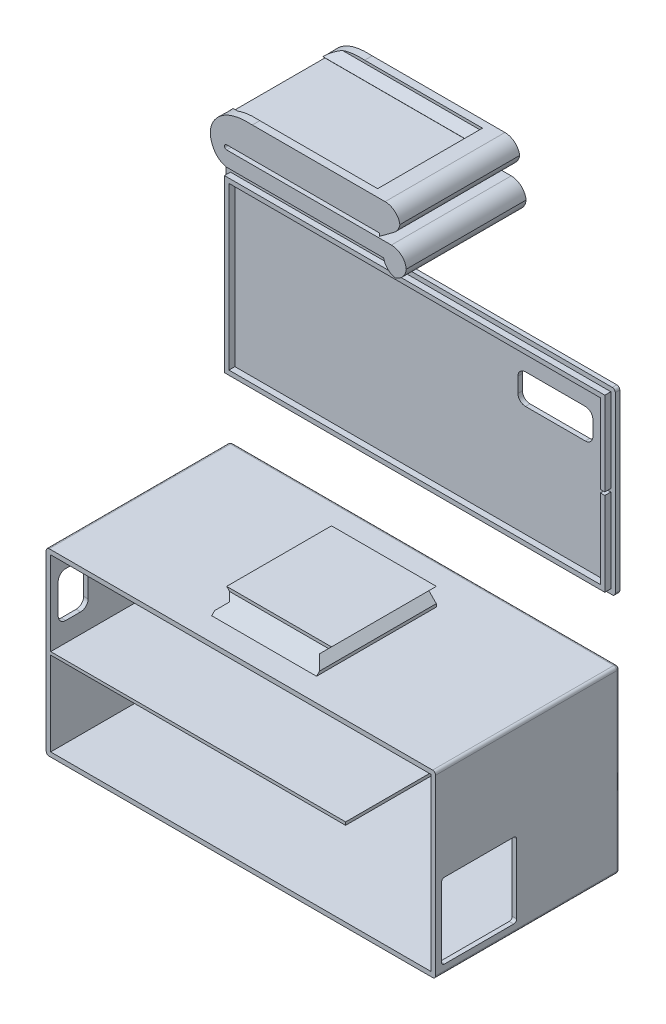
SolidWorks part; units mm, degrees
ref_plane "Alzado" through (0, 0, 0) normal (1, 0, 0) x (0, 1, 0)
ref_plane "Planta" through (0, 0, 0) normal (0, 0, 1) x (0, 1, 0)
ref_plane "Vista lateral" through (0, 0, 0) normal (0, 1, 0) x (-1, 0, 0)
sketch "Croquis1" plane through (0, 0, 0) normal (0, 0, 1) x (0, 1, 0)
  line L0 (0.5, 65) -> (0.5, -65) construction
  line L1 (30, -65) -> (-30, -65)
  line L2 (30, -65) -> (30, 65)
  line L3 (30, 65) -> (-30, 65)
  line L4 (-30, -65) -> (-30, 65)
  line L5 (30, -65) -> (-30, 65) construction
  line L6 (30, 65) -> (-30, -65) construction
  line L7 (-0.5, -65) -> (-0.5, 65) construction
  point P0 (0, 0)
  dimension "D1" = 60
  dimension "D2" = 130
  dimension "D3" = 1
  dimension "D4" = 29.5
extrude "Saliente-Extruir1" add sketch "Croquis1" along normal blind 1.5
sketch "Croquis2" plane through (0, 0, 1.5) normal (0, 0, 1) x (1, 0, 0)
  line L4 (-63.5, 0.5) -> (63.5, 0.5)
  line L5 (-63.5, -0.5) -> (63.5, -0.5)
  line L6 (-63.5, 28.5) -> (-63.5, 0.5)
  line L7 (-63.5, -28.5) -> (63.5, -28.5)
  line L8 (65, -30) -> (65, 30)
  line L9 (-65, -30) -> (65, -30)
  line L10 (-65, 30) -> (-65, -30)
  line L11 (65, 30) -> (-65, 30)
  line L12 (65, -30) -> (65, 30)
  line L13 (-65, -30) -> (65, -30)
  line L14 (-65, 30) -> (-65, -30)
  line L15 (65, 30) -> (-65, 30)
  line L16 (63.5, -28.5) -> (63.5, -0.5)
  line L17 (63.5, 28.5) -> (-63.5, 28.5)
  line L18 (-63.5, -0.5) -> (-63.5, -28.5)
  line L19 (63.5, 0.5) -> (63.5, 28.5)
  line L20 (-63.5, 28.5) -> (-63.5, -28.5) construction
  line L22 (63.5, -28.5) -> (63.5, 28.5) construction
  dimension "D3" = 1
  dimension "D1" = 0
  dimension "D2" = 1.5
extrude "Saliente-Extruir2" add sketch "Croquis2" along normal blind 60
sketch "Croquis3" plane through (0, 0.5, 0) normal (0, 1, 0) x (-1, 0, 0)
  line L1 (-63.5, 61.5) -> (-34.9603, 61.5)
  line L2 (-63.5, 61.5) -> (-63.5, 31.5)
  line L3 (-53.5, 21.5) -> (-44.9603, 21.5)
  line L4 (-34.9603, 61.5) -> (-34.9603, 31.5)
  arc A0 (-63.5, 31.5) -> (-53.5, 21.5) centre (-53.5, 31.5) ccw
  arc A1 (-44.9603, 21.5) -> (-34.9603, 31.5) centre (-44.9603, 31.5) ccw
  point P9 (-34.9603, 21.5)
  dimension "D2" = 10
  dimension "D1" = 40
extrude "Cortar-Extruir1" cut sketch "Croquis3" against normal blind 2
sketch "Croquis4" plane through (0, 0, 1.5) normal (0, 0, 1) x (1, 0, 0)
  line L0 (-63.5, -6.5) -> (63.5, -6.5)
  line L4 (-63.5, -0.5) -> (-63.5, -28.5) construction
  line L5 (63.5, -28.5) -> (63.5, 28.5) construction
  line L6 (34.9603, -0.5) -> (-63.5, -0.5) construction
  line L7 (-63.5, -8.1) -> (63.5, -8.1)
  line L8 (-63.5, -6.5) -> (-63.5, -0.5)
  line L9 (-63.5, -0.5) -> (63.5, -0.5)
  line L10 (63.5, -0.5) -> (63.5, -6.5)
  line L11 (-63.5, -8.1) -> (-63.5, -28.5)
  line L12 (-63.5, -28.5) -> (63.5, -28.5)
  line L13 (63.5, -28.5) -> (63.5, -8.1)
  dimension "D1" = 6
  dimension "D2" = 1.6
extrude "Saliente-Extruir3" add sketch "Croquis4" along normal blind 3
sketch "Croquis5" plane through (-65, 0, 0) normal (-1, 0, 0) x (0, -1, 0)
  line L0 (-14.5, 1.5) -> (-14.5, 61.5) construction
  line L1 (-28.5, 1.5) -> (-0.5, 1.5) construction
  line L2 (-30, 61.5) -> (30, 61.5) construction
  line L4 (-9.5, 49) -> (-19.5, 49)
  line L5 (-7, 51.5) -> (-7, 56.5)
  line L6 (-9.5, 59) -> (-19.5, 59)
  line L7 (-22, 51.5) -> (-22, 56.5)
  line L8 (-7, 49) -> (-22, 59) construction
  line L9 (-7, 59) -> (-22, 49) construction
  arc A0 (-19.5, 49) -> (-22, 51.5) centre (-19.5, 51.5) cw
  arc A1 (-9.5, 49) -> (-7, 51.5) centre (-9.5, 51.5) ccw
  arc A2 (-7, 56.5) -> (-9.5, 59) centre (-9.5, 56.5) ccw
  arc A3 (-19.5, 59) -> (-22, 56.5) centre (-19.5, 56.5) ccw
  point P6 (-14.5, 54)
  dimension "D4" = 2.5
  dimension "D1" = 52.5
  dimension "D2" = 15
  dimension "D3" = 10
extrude "Cortar-Extruir2" cut sketch "Croquis5" against normal blind 3
sketch "Croquis6" plane through (0, 0, 0) normal (0, 0, 1) x (0, 1, 0)
  line L1 (110.6539, -65) -> (50.6539, -65)
  line L2 (110.6539, -65) -> (110.6539, 65)
  line L3 (110.6539, 65) -> (50.6539, 65)
  line L4 (50.6539, -65) -> (50.6539, 65)
  line L5 (110.6539, -65) -> (50.6539, 65) construction
  line L6 (110.6539, 65) -> (50.6539, -65) construction
  point P0 (80.6539, 0)
  dimension "D1" = 60
  dimension "D2" = 130
extrude "Saliente-Extruir4" add sketch "Croquis6" along normal blind 1.5 separate body
sketch "Croquis7" plane through (0, 0, 1.5) normal (0, 0, 1) x (1, 0, 0)
  line L4 (62, 107.6539) -> (-62, 107.6539)
  line L5 (-62, 107.6539) -> (-62, 53.6539)
  line L6 (-62, 53.6539) -> (62, 53.6539)
  line L7 (62, 53.6539) -> (62, 107.6539)
  line L8 (-63.5, 52.1539) -> (63.5, 52.1539)
  line L9 (63.5, 52.1539) -> (63.5, 109.1539)
  line L10 (63.5, 109.1539) -> (-63.5, 109.1539)
  line L11 (-63.5, 109.1539) -> (-63.5, 52.1539)
  line L12 (-63.5, 52.1539) -> (63.5, 52.1539)
  line L13 (63.5, 52.1539) -> (63.5, 109.1539)
  line L14 (63.5, 109.1539) -> (-63.5, 109.1539)
  line L15 (-63.5, 109.1539) -> (-63.5, 52.1539)
  dimension "D1" = 1.5
  dimension "D2" = 1.5
extrude "Saliente-Extruir5" add sketch "Croquis7" along normal blind 2
sketch "Croquis8" plane through (0, 0, 0) normal (0, 0, -1) x (1, 0, 0)
  line L1 (55, -100.6539) -> (35, -100.6539)
  line L2 (57.5, -98.1539) -> (57.5, -93.1539)
  line L3 (55, -90.6539) -> (35, -90.6539)
  line L4 (32.5, -98.1539) -> (32.5, -93.1539)
  line L5 (57.5, -100.6539) -> (32.5, -90.6539) construction
  line L6 (57.5, -90.6539) -> (32.5, -100.6539) construction
  line L7 (65, -110.6539) -> (-65, -110.6539) construction
  line L8 (65, -50.6539) -> (65, -110.6539) construction
  arc A0 (35, -100.6539) -> (32.5, -98.1539) centre (35, -98.1539) cw
  arc A1 (55, -100.6539) -> (57.5, -98.1539) centre (55, -98.1539) ccw
  arc A2 (57.5, -93.1539) -> (55, -90.6539) centre (55, -93.1539) ccw
  arc A3 (35, -90.6539) -> (32.5, -93.1539) centre (35, -93.1539) ccw
  point P0 (45, -95.6539)
  dimension "D5" = 2.5
  dimension "D1" = 25
  dimension "D2" = 10
  dimension "D3" = 15
  dimension "D4" = 20
extrude "Cortar-Extruir3" cut sketch "Croquis8" against normal blind 2
sketch "Croquis9" plane through (0, 0, 3.5) normal (0, 0, 1) x (1, 0, 0)
  line L0 (62, 53.6539) -> (62, 107.6539) construction
  line L4 (63.5, 80.1439) -> (63.5, 81.1639)
  line L5 (62, 80.6539) -> (63.5, 81.1639) construction
  line L6 (62, 80.6539) -> (63.5, 80.1439) construction
  line L7 (63.5, 52.1539) -> (63.5, 109.1539) construction
  line L8 (63.5, 80.1439) -> (62, 80.1439)
  line L9 (62, 80.1439) -> (62, 81.1639)
  line L10 (62, 81.1639) -> (63.5, 81.1639)
  line L11 (62, 80.6539) -> (63.5, 80.6539) construction
  point P0 (62, 80.6539)
  dimension "D1" = 0.51
  dimension "D2" = 0.51
extrude "Cortar-Extruir4" cut sketch "Croquis9" against normal blind 2
sketch "Croquis10" plane through (65, 0, 0) normal (1, 0, 0) x (0, 1, 0)
  line L0 (-14.5, 61.5) -> (-14.5, 4.5) construction
  line L1 (-30, 61.5) -> (30, 61.5) construction
  line L2 (-28.5, 4.5) -> (-8.1, 4.5) construction
  line L3 (-0.5, 61.5) -> (-0.5, 31.5) construction
  line L6 (-2.95, 34.4139) -> (-26.05, 34.4139)
  line L7 (-1.95, 35.4139) -> (-1.95, 58.5139)
  line L8 (-2.95, 59.5139) -> (-26.05, 59.5139)
  line L9 (-27.05, 35.4139) -> (-27.05, 58.5139)
  line L10 (-1.95, 34.4139) -> (-27.05, 59.5139) construction
  line L11 (-1.95, 59.5139) -> (-27.05, 34.4139) construction
  arc A0 (-26.05, 34.4139) -> (-27.05, 35.4139) centre (-26.05, 35.4139) cw
  arc A1 (-2.95, 34.4139) -> (-1.95, 35.4139) centre (-2.95, 35.4139) ccw
  arc A2 (-1.95, 58.5139) -> (-2.95, 59.5139) centre (-2.95, 58.5139) ccw
  arc A3 (-26.05, 59.5139) -> (-27.05, 58.5139) centre (-26.05, 58.5139) ccw
  point P8 (-14.5, 46.9639)
  dimension "D4" = 1
  dimension "D1" = 14
  dimension "D2" = 25.1
  dimension "D3" = 25.1
extrude "Cortar-Extruir5" cut sketch "Croquis10" against normal blind 2
fillet "Redondeo1" radius 1 8 edges at (65, 0, 0) (0, 30, 0) (-65, 0, 0) (0, -30, 0) (-65, -30, 30.75) (-65, 30, 30.75) (65, 30, 30.75) (65, -30, 30.75)
fillet "Redondeo2" radius 1 4 edges at (-65, 50.6539, 0.75) (-65, 110.6539, 0.75) (65, 50.6539, 0.75) (65, 110.6539, 0.75)
sketch "Croquis11" plane through (0, 30, 0) normal (0, 1, 0) x (-1, 0, 0)
  line L1 (17.5, 13.75) -> (-17.5, 13.75)
  line L2 (17.5, 13.75) -> (17.5, 48.75)
  line L3 (17.5, 48.75) -> (-17.5, 48.75)
  line L4 (-17.5, 13.75) -> (-17.5, 48.75)
  line L5 (17.5, 13.75) -> (-17.5, 48.75) construction
  line L6 (17.5, 48.75) -> (-17.5, 13.75) construction
  line L7 (-64, 61.5) -> (-64, 1) construction
  point P0 (0, 31.25)
  point P5 (0, 0)
  point P6 (0, 0)
  point P9 (-64, 31.25)
  point P10 (0, 0)
  dimension "D1" = 35
  dimension "D2" = 35
extrude "Saliente-Extruir8" add sketch "Croquis11" along normal blind 6
sketch "Croquis15" plane through (0, 0, 48.75) normal (0, 0, 1) x (1, 0, 0)
  line L3 (0, 36) -> (0, 30) construction
  line L4 (-17.5, 36) -> (17.5, 36) construction
  line L5 (-17.5, 30) -> (17.5, 30) construction
  line L6 (-17.5, 31) -> (17.5, 31) construction
  line L7 (-17.5, 36) -> (-17.5, 30) construction
  line L8 (17.5, 36) -> (17.5, 30) construction
  line L9 (64, 30) -> (-64, 30) construction
  line L10 (-17.5, 36) -> (-15, 33.5)
  line L11 (-15, 33.5) -> (-17.5, 31)
  line L12 (-17.5, 31) -> (-17.5, 36)
  dimension "D1" = 1
  dimension "D2" = 2.5
  dimension "D3" = 2.5
extrude "Cortar-Extruir7" cut sketch "Croquis15" against normal blind 45
mirror "Simetría1" about plane through (0, 0, 0) normal (1, 0, 0) of "Cortar-Extruir7"
chamfer "Chaflán1" distance 5 angle 45 1 edges at (0, 30, 48.75)
sketch "Croquis16" plane through (0, 0, 0) normal (0, 0, 1) x (0, 1, 0)
  line L0 (153.4307, 31.6933) -> (153.4307, -33.7427) construction
  line L1 (153.4307, 26.2573) -> (153.4307, -33.7427)
  line L6 (148.4307, 26.2573) -> (148.4307, -26.1461)
  line L7 (153.4307, -33.7427) -> (148.4307, -33.7427)
  line L8 (154.9307, 26.2573) -> (154.9307, -24.7427)
  line L9 (154.9307, -24.7427) -> (153.9307, -24.7427)
  line L10 (153.9307, -24.7427) -> (159.062, -31.6504)
  line L11 (159.062, -31.6504) -> (164.9307, -31.6504)
  line L12 (164.9307, -31.6504) -> (164.9307, 17.6885)
  line L13 (148.4307, 31.6933) -> (148.4307, -33.7427) construction
  line L15 (148.4307, -26.1461) -> (144.4307, -26.1461)
  line L17 (148.4307, -33.7427) -> (144.4307, -33.7427)
  line L18 (144.4307, -26.1461) -> (144.4307, -33.7427)
  arc A0 (154.9307, 26.2573) -> (153.4307, 26.2573) centre (154.1807, 26.2573) ccw
  spline S0 degree 3 poles (148.4307, 26.2573) (148.9126, 29.2128) (152.0108, 31.3039) (159.3944, 32.2769) (165.5706, 27.2876) (164.9307, 17.6885) knots 0 0 0 0 0.351905 0.430581 1 1 1 1
  dimension "D3" = 51
  dimension "D4" = 1.5
  dimension "D1" = 60
  dimension "D5" = 0.5
  dimension "D6" = 10
  dimension "D7" = 4
  dimension "D2" = 5
extrude "Saliente-Extruir9" add sketch "Croquis16" along normal blind 40 separate body
sketch "Croquis17" plane through (31.6504, 0, 0) normal (1, 0, 0) x (0, 1, 0)
  line L0 (164.0307, 40) -> (164.0307, 0) construction
  line L2 (159.062, 0) -> (164.9307, 0) construction
  line L3 (164.9307, 40) -> (164.9307, 0) construction
  line L8 (159.062, 20) -> (164.9824, 20) construction
  line L9 (159.062, 40) -> (159.062, 0) construction
  line L10 (164.9824, 0) -> (164.9824, 40) construction
  line L14 (164.0307, 37.5) -> (158.9307, 37.5) construction
  line L15 (158.9307, 37.5) -> (161.4807, 34.99)
  line L16 (161.4807, 34.99) -> (164.0307, 37.5)
  line L18 (164.0307, 2.5) -> (158.9307, 2.5) construction
  line L19 (158.9307, 2.5) -> (161.4807, 5.01)
  line L20 (161.4807, 5.01) -> (164.0307, 2.5)
  line L21 (158.9307, 37.5) -> (158.9307, 2.5)
  line L22 (164.0307, 2.5) -> (164.0307, 37.5) construction
  line L23 (164.0307, 37.5) -> (168.4127, 37.5)
  line L24 (168.4127, 37.5) -> (168.4127, 2.5)
  line L25 (168.4127, 2.5) -> (164.0307, 2.5)
  dimension "D1" = 0.9
  dimension "D2" = 5.1
  dimension "D3" = 2.51
  dimension "D4" = 17.5
  dimension "D5" = 2.55
extrude "Cortar-Extruir8" cut sketch "Croquis17" against normal blind 60 from offset 10 offset against normal yes
fillet "Redondeo3" radius 5 5 edges at (26.1461, 144.4307, 20) (33.7427, 144.4307, 20) (33.7427, 153.4307, 20) (31.6504, 164.9307, 20) (31.6504, 159.062, 20)
